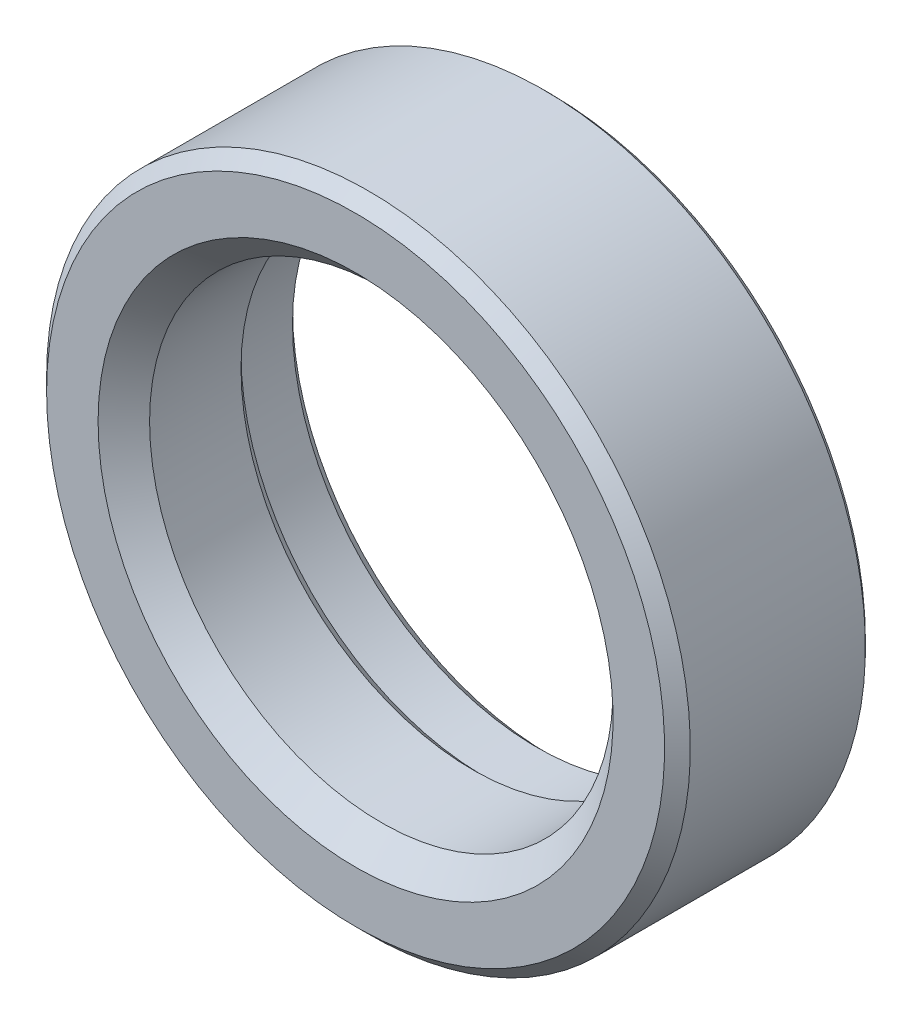
SolidWorks part; units mm, degrees
ref_plane "Alzado" through (0, 0, 0) normal (0, 0, 1) x (1, 0, 0)
ref_plane "Planta" through (0, 0, 0) normal (0, 1, 0) x (1, 0, 0)
ref_plane "Vista lateral" through (0, 0, 0) normal (1, 0, 0) x (0, 0, -1)
sketch "Croquis1" plane through (0, 0, 0) normal (1, 0, 0) x (0, 0, -1)
  line L0 (-5.5053, 0) -> (7.5947, 0)
  line L1 (-7.5053, 2) -> (-7.5053, 6)
  line L2 (-6.5053, 7) -> (7.5947, 7)
  line L3 (7.5947, 7) -> (7.5947, 0)
  line L4 (7.5947, -18) -> (-7.5053, -18) construction
  line L5 (-7.5053, 2) -> (-5.5053, 0)
  line L6 (-7.5053, 6) -> (-6.5053, 7)
  point P0 (-7.5053, 0)
  point P4 (-7.5053, 7)
  dimension "D1" = 15.1
  dimension "D2" = 7
  dimension "D3" = 18
revolve "Revolución2" add sketch "Croquis1" angle 360 about L4
sketch "Croquis4" plane through (0, 0, -7.5947) normal (0, 0, -1) x (-1, 0, 0)
  line L0 (-25, -18) -> (25, -18) construction
  line L1 (0, 7) -> (0, -43) construction
  circle A0 centre (0, -18) radius 25 construction
  circle A1 centre (0, -18) radius 19
extrude "Cortar-Extruir1" cut sketch "Croquis4" against normal blind 5
chamfer "Chaflán1" distance 1 angle 45 1 edges at (-18, -18, -2.5947)
chamfer "Chaflán2" distance 0.5 angle 45 1 edges at (-25, -18, -7.5947)
chamfer "Chaflán3" distance 1 angle 45 1 edges at (-19, -18, -7.5947)
sketch "Croquis5" plane through (0, 0, -7.5947) normal (0, 0, -1) x (-1, 0, 0)
  circle A0 centre (0, 4) radius 1.25
  circle A1 centre (0, -18) radius 24.5 construction
  circle A2 centre (11, 1.0526) radius 1.25
  circle A3 centre (19.0526, -7) radius 1.25
  circle A4 centre (22, -18) radius 1.25
  circle A5 centre (19.0526, -29) radius 1.25
  circle A6 centre (11, -37.0526) radius 1.25
  circle A7 centre (0, -40) radius 1.25
  circle A8 centre (-11, -37.0526) radius 1.25
  circle A9 centre (-19.0526, -29) radius 1.25
  circle A10 centre (-22, -18) radius 1.25
  circle A11 centre (-19.0526, -7) radius 1.25
  circle A12 centre (-11, 1.0526) radius 1.25
  point P29 (0, -18)
  dimension "D1" = 22
  dimension "D2" = 12
extrude "Cortar-Extruir2" cut sketch "Croquis5" against normal blind 7.5
chamfer "Chaflán4" distance 0.2 angle 45 12 edges at (17.8026, -29, -7.5947) (9.75, -37.0526, -7.5947) (-1.25, -40, -7.5947) (-12.25, -37.0526, -7.5947) (-20.3026, -29, -7.5947) (-23.25, -18, -7.5947) (-20.3026, -7, -7.5947) (-12.25, 1.0526, -7.5947) (-1.25, 4, -7.5947) (9.75, 1.0526, -7.5947) (17.8026, -7, -7.5947) (20.75, -18, -7.5947)
